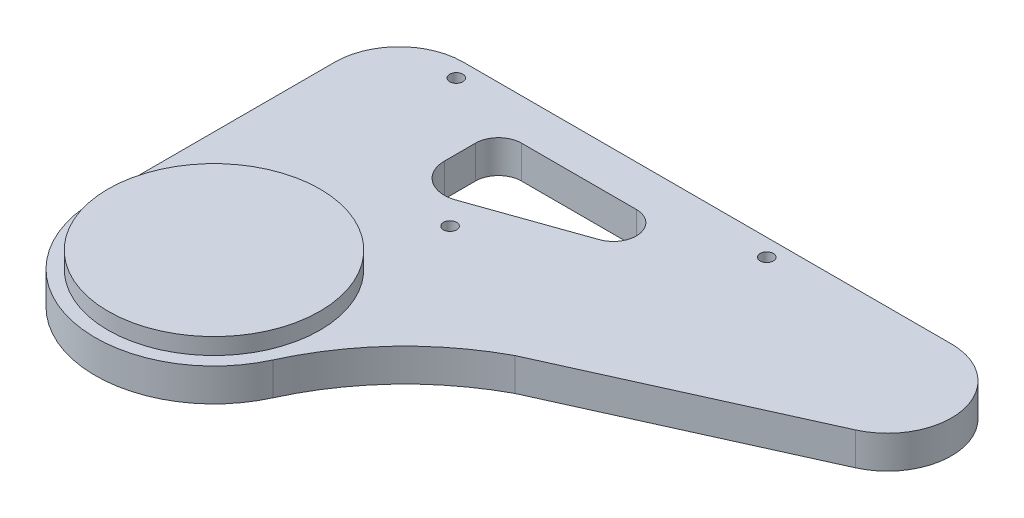
SolidWorks part; units mm, degrees
ref_plane "Front Plane" through (0, 0, 0) normal (0, 0, 1) x (1, 0, 0)
ref_plane "Top Plane" through (0, 0, 0) normal (0, 1, 0) x (1, 0, 0)
ref_plane "Right Plane" through (0, 0, 0) normal (1, 0, 0) x (0, 0, -1)
sketch "Sketch2" plane through (0, 0, 0) normal (0, 1, 0) x (1, 0, 0)
  line L0 (-168.1647, -50) -> (-168.1647, 0)
  line L1 (-148.6647, 19.5) -> (0.2358, 19.5)
  line L2 (-63.4089, -50) -> (8.0195, -17.7762)
  line L3 (-168.1647, -50) -> (-63.4089, -50) construction
  line L4 (-125.4, 0) -> (-125.4, -9.5)
  line L5 (-113.4064, -17.9876) -> (-81.1217, -6.6008)
  line L6 (-118.4, 7) -> (-83.3525, 7)
  line L7 (0, 0) -> (-119.5453, 0) construction
  line L8 (-168.1647, -50) -> (-168.1647, -73)
  arc A0 (-168.1647, 0) -> (-148.6647, 19.5) centre (-148.6647, 0) cw
  arc A1 (8.0195, -17.7762) -> (0.2358, 19.5) centre (0, 0) ccw
  circle A2 centre (-145.5033, 14.25) radius 2
  circle A3 centre (-107.4, -25.75) radius 2
  circle A4 centre (-51.0033, 14.25) radius 2
  arc A5 (-125.4, 0) -> (-118.4, 7) centre (-118.4, 0) cw
  arc A6 (-125.4, -9.5) -> (-113.4064, -17.9876) centre (-116.4, -9.5) ccw
  arc A7 (-81.1217, -6.6008) -> (-83.3525, 7) centre (-83.45, 0.0007) ccw
  circle A8 centre (-132, -73) radius 32.25
  arc A9 (-168.1647, -73) -> (-99.0922, -87.9986) centre (-132, -73) ccw
  arc A10 (-99.0922, -87.9986) -> (-63.4089, -50) centre (-25.1126, -121.7166) cw
  dimension "D4" = 19.5014
  dimension "D13" = 24.282
  dimension "D14" = 7
  dimension "D15" = 7
  dimension "D16" = 9
  dimension "D19" = 4
  dimension "D20" = 64.5
  dimension "D1" = 25.75
  dimension "D2" = 14.25
  dimension "D3" = 19.5
  dimension "D5" = 94.5
  dimension "D6" = 148.6647
  dimension "D7" = 107.4
  dimension "D8" = 83.45
  dimension "D9" = 51.0033
  dimension "D10" = 116.4
  dimension "D11" = 118.4
  dimension "D12" = 50
  dimension "D17" = 9.5
  dimension "D18" = 35.0475
  dimension "D21" = 132
  dimension "D22" = 73
extrude "Boss-Extrude1" add sketch "Sketch2" against normal blind 10 contours A9 A10 L2 A1 L1 A0 L0 L8 A2 A3 A4 A7 L5 A6 L4 A5 L6 A8 | A8 region at (-83.9152, 0, 18.7656) region at (-132, 0, 73)
extrude "Boss-Extrude2" add sketch "Sketch2<3>" along normal blind 5 contours A8 region at (-132, 0, 73)
sketch "Sketch2<3>" plane through (0, 0, 0) normal (0, 1, 0) x (1, 0, 0) same geometry as "Sketch2"
sketch "Sketch3" plane through (0, 0, 0) normal (0, 1, 0) x (1, 0, 0)
  line L0 (0, 0) -> (0, 70.5559) construction
  line L1 (0, 0) -> (-231.9765, -93.7246) construction
  line L2 (0, 0) -> (-202.4118, -147.0608) construction
  line L3 (0, 0) -> (-218.8043, -121.2852) construction
  line L4 (-187.0919, 0) -> (43.2105, 0) construction
  point P9 (-218.8043, -121.2852)
  point P10 (-202.4118, -147.0608)
  dimension "D1" = 112
  dimension "D2" = 234
  dimension "D3" = 29
